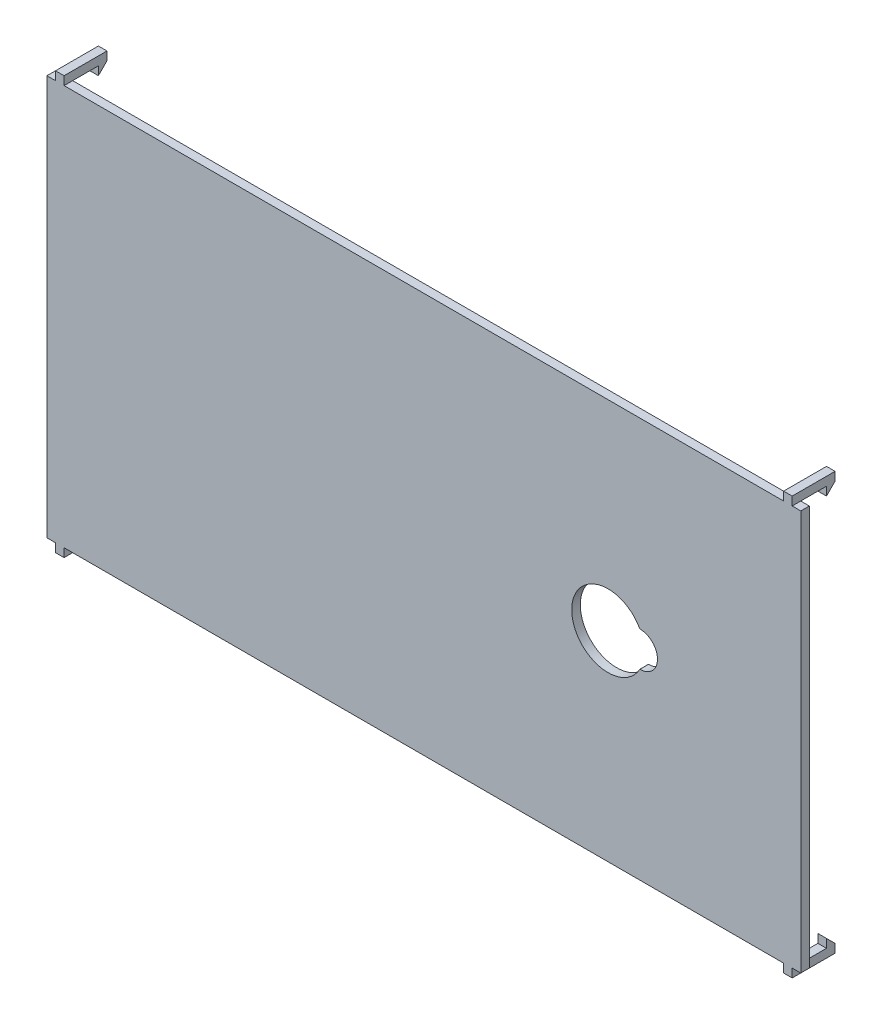
SolidWorks part; units mm, degrees
ref_plane "Front Plane" through (0, 0, 0) normal (0, 0, 1) x (1, 0, 0)
ref_plane "Top Plane" through (0, 0, 0) normal (0, 1, 0) x (1, 0, 0)
ref_plane "Right Plane" through (0, 0, 0) normal (1, 0, 0) x (0, 0, -1)
sketch "Sketch1" plane through (0, 0, 0) normal (0, 0, 1) x (1, 0, 0)
  line L0 (121.1, -9.75) -> (-10.75, -9.75)
  line L1 (119.6, -8.25) -> (-9.25, -8.25)
  line L2 (119.6, -8.25) -> (119.6, 58.75)
  line L3 (119.6, 58.75) -> (-9.25, 58.75)
  line L4 (-9.25, -8.25) -> (-9.25, 58.75)
  line L5 (-10.75, -9.75) -> (-10.75, 60.25)
  line L6 (121.1, 60.25) -> (-10.75, 60.25)
  line L7 (121.1, -9.75) -> (121.1, 60.25)
  dimension "D1" = 1.5
extrude "Boss-Extrude1" add sketch "Sketch1" along normal blind 1.5 contours L7 L6 L5 L0
sketch "Sketch2" plane through (0, 0, 1.5) normal (0, 0, 1) x (1, 0, 0)
  line L5 (92.9571, 22.2) -> (92.9875, 22.2)
  line L6 (92.9875, 28.3) -> (92.9571, 28.3)
  line L7 (92.9571, 22.2) -> (92.9875, 22.2)
  line L8 (92.9875, 28.3) -> (92.9571, 28.3)
  arc A10 (92.9875, 22.2) -> (92.9875, 28.3) centre (92.9875, 25.25) ccw
  arc A11 (92.9571, 28.3) -> (92.9571, 22.2) centre (87.3875, 25.25) ccw
  arc A12 (92.9875, 22.2) -> (92.9875, 28.3) centre (92.9875, 25.25) ccw
  arc A13 (92.9571, 28.3) -> (92.9571, 22.2) centre (87.3875, 25.25) ccw
  dimension "D1" = 0.25
extrude "Cut-Extrude1" cut sketch "Sketch2" against normal up to next
ref_plane "Plane2" through (0, 25.25, 0) normal (0, 1, 0) x (1, 0, 0)
ref_plane "Plane1" through (55.175, 0, 0) normal (1, 0, 0) x (0, 0, -1)
sketch "Sketch3" plane through (121.1, 0, 0) normal (1, 0, 0) x (0, 0, -1)
  line L0 (0, -9.75) -> (0, 60.25) construction
  line L1 (-1.5, 60.25) -> (6, 60.25)
  line L2 (-1.5, 60.25) -> (-1.5, 61.75)
  line L3 (-1.5, 61.75) -> (6, 61.75)
  line L4 (6, 60.25) -> (6, 61.75)
  line L5 (6, 60.25) -> (4.5, 58.75)
  line L7 (4.5, 58.75) -> (4.5, 60.25)
  line M6 (0, 60.25) -> (-1.5, 60.25)
  dimension "D1" = 1.5
  dimension "D2" = 6
  dimension "D3" = 45
extrude "Boss-Extrude2" add sketch "Sketch3" against normal blind 1.5 from offset 1.5 contours L1 L4 L3 L2 M6 | L7 L5 L1 region at (121.1, 61, -2.25) region at (121.1, 59.75, -5) offset against normal yes
mirror "Mirror1" about plane through (55.175, 0, 0) normal (1, 0, 0) of "Boss-Extrude2"
mirror "Mirror2" about plane through (0, 25.25, 0) normal (0, 1, 0) of "Mirror1", "Boss-Extrude2"
